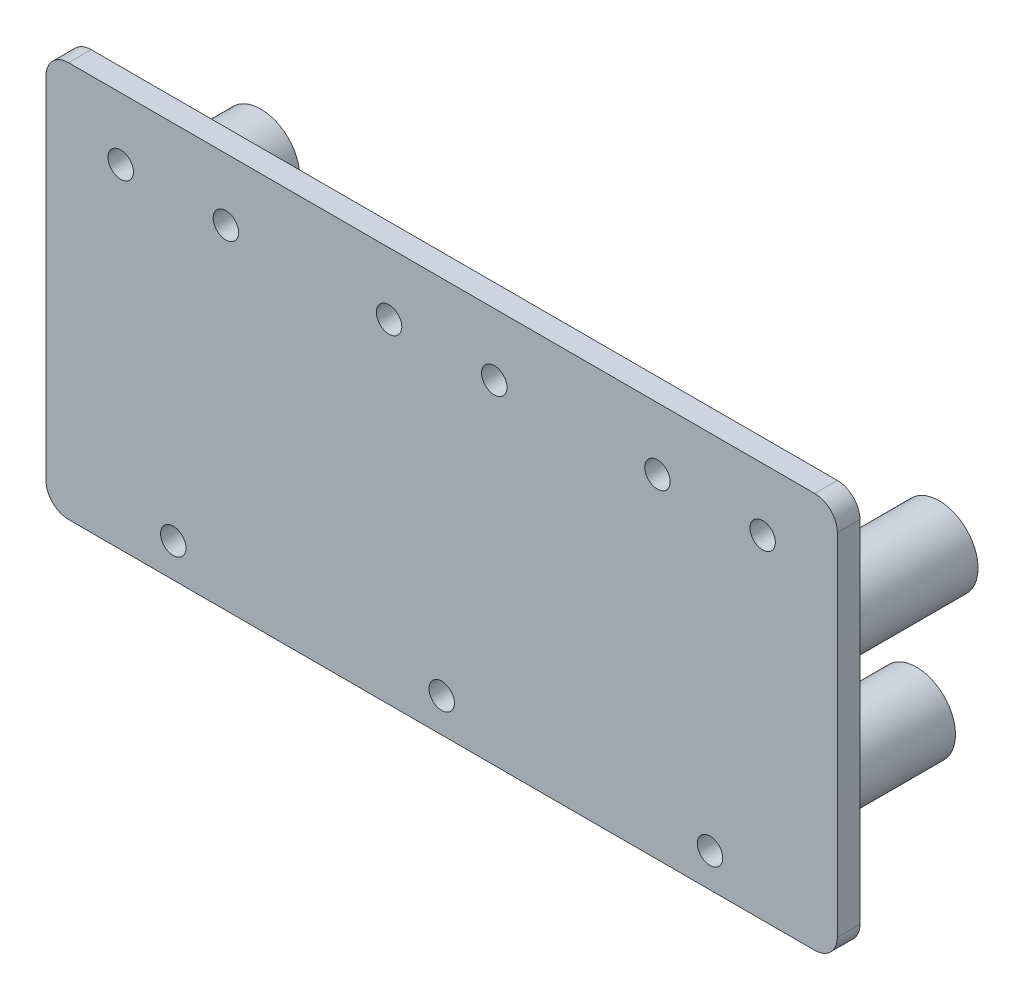
SolidWorks part; units mm, degrees
ref_plane "Front Plane" through (0, 0, 0) normal (0, 0, 1) x (1, 0, 0)
ref_plane "Top Plane" through (0, 0, 0) normal (0, 1, 0) x (1, 0, 0)
ref_plane "Right Plane" through (0, 0, 0) normal (1, 0, 0) x (0, 0, -1)
sketch "Sketch1" plane through (0, 0, 0) normal (0, 0, 1) x (1, 0, 0)
  line L1 (-33, -17.5) -> (33, -17.5)
  line L2 (-35, -15.5) -> (-35, 15.5)
  line L3 (-33, 17.5) -> (33, 17.5)
  line L4 (35, -15.5) -> (35, 15.5)
  line L5 (-35, -17.5) -> (35, 17.5) construction
  line L6 (-35, 17.5) -> (35, -17.5) construction
  arc A0 (-33, -17.5) -> (-35, -15.5) centre (-33, -15.5) cw
  arc A1 (33, -17.5) -> (35, -15.5) centre (33, -15.5) ccw
  arc A2 (33, 17.5) -> (35, 15.5) centre (33, 15.5) cw
  arc A3 (-35, 15.5) -> (-33, 17.5) centre (-33, 15.5) cw
  point P0 (0, 0)
  dimension "D3" = 2
  dimension "D1" = 35
  dimension "D2" = 70
extrude "Boss-Extrude1" add sketch "Sketch1" along normal blind 2
sketch "Sketch2" plane through (0, 0, 0) normal (0, 0, -1) x (-1, 0, 0)
  line L0 (0, 0) -> (-50000, 0) construction
  line L1 (0, 0) -> (0, -50000) construction
  line L2 (28, 0) -> (28, -17.5) construction
  line L3 (33, -17.5) -> (-33, -17.5) construction
  line L4 (-28, 0) -> (-28, -17.5) construction
  line L5 (-30, 17.5) -> (-30, 0) construction
  line L6 (-33, 17.5) -> (33, 17.5) construction
  circle A0 centre (28, -8.75) radius 1.95
  circle A1 centre (-28, -8.75) radius 1.95
  circle A2 centre (-30, 5) radius 1.95
  circle A3 centre (30, 5) radius 1.95
  circle A4 centre (28, -8.75) radius 3.45
  circle A5 centre (30, 5) radius 3.45
  circle A6 centre (-30, 5) radius 3.45
  circle A7 centre (-28, -8.75) radius 3.45
  point P17 (28, -8.75)
  point P20 (-28, -8.75)
  dimension "D3" = 3.9
  dimension "D1" = 28
  dimension "D2" = 28
  dimension "D4" = 30
  dimension "D5" = 30
  dimension "D7" = 5
  dimension "D6" = 1.5
extrude "Boss-Extrude2" add sketch "Sketch2" along normal blind 12
sketch "Sketch3" plane through (0, 0, 2) normal (0, 0, 1) x (1, 0, 0)
  circle A0 centre (-23.74, -14.5) radius 1.125 construction
  circle A1 centre (0, -14.5) radius 1.125 construction
  circle A2 centre (23.74, -14.5) radius 1.125 construction
  circle A3 centre (-23.74, -14.5) radius 1.125
  circle A4 centre (0, -14.5) radius 1.125
  circle A5 centre (23.74, -14.5) radius 1.125
  circle A6 centre (-19.0867, 11.9993) radius 1.125 construction
  circle A7 centre (-28.3933, 11.9993) radius 1.125 construction
  circle A8 centre (-19.0867, 11.9993) radius 1.125
  circle A9 centre (-28.3933, 11.9993) radius 1.125
  circle A10 centre (-4.6533, 11.9993) radius 1.125 construction
  circle A11 centre (4.6533, 11.9993) radius 1.125 construction
  circle A12 centre (-4.6533, 11.9993) radius 1.125
  circle A13 centre (4.6533, 11.9993) radius 1.125
  circle A14 centre (19.0867, 11.9993) radius 1.125 construction
  circle A15 centre (28.3933, 11.9993) radius 1.125 construction
  circle A16 centre (19.0867, 11.9993) radius 1.125
  circle A17 centre (28.3933, 11.9993) radius 1.125
extrude "Cut-Extrude1" cut sketch "Sketch3" against normal through all both and the other way through all
